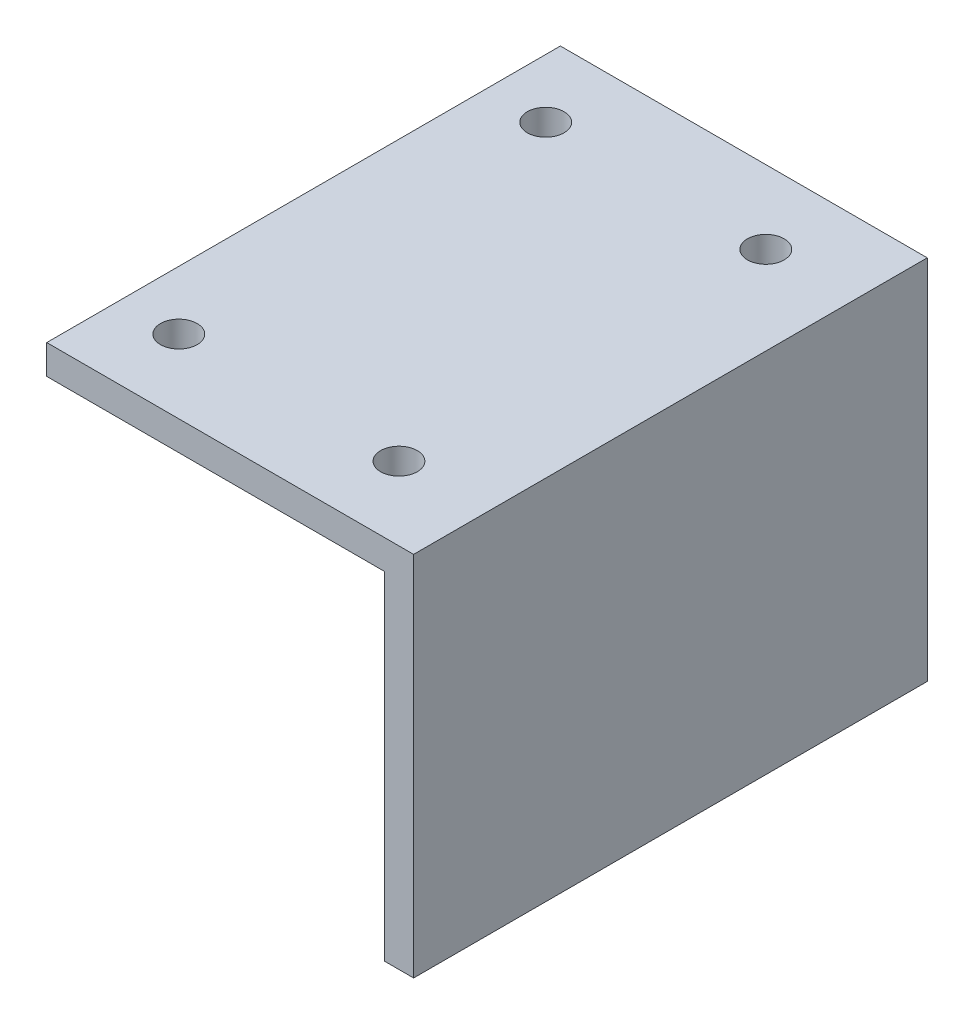
SolidWorks part; units mm, degrees
ref_plane "Alzado" through (0, 0, 0) normal (0, 0, 1) x (1, 0, 0)
ref_plane "Planta" through (0, 0, 0) normal (0, 1, 0) x (1, 0, 0)
ref_plane "Vista lateral" through (0, 0, 0) normal (1, 0, 0) x (0, 0, -1)
sketch "Croquis2" plane through (0, 0, 0) normal (0, 0, 1) x (1, 0, 0)
  line L0 (0, 0) -> (-50, 0)
  line L1 (0, 0) -> (0, -50)
  line L2 (-4, -4) -> (-4, -50)
  line L3 (-4, -4) -> (-50, -4)
  line L4 (-50, 0) -> (-50, -4)
  line L5 (-4, -50) -> (0, -50)
  dimension "D1" = 50
  dimension "D2" = 4
extrude "Saliente-Extruir1" add sketch "Croquis2" along normal blind 35 and the other way blind 35
sketch "Croquis3" plane through (0, -4, 0) normal (0, -1, 0) x (1, 0, 0)
  line L0 (-4, 0) -> (-50, 0) construction
  line L1 (-42, 25) -> (-12, 25) construction
  line L2 (-42, 25) -> (-42, -25) construction
  line L3 (-42, -25) -> (-12, -25) construction
  line L4 (-12, 25) -> (-12, -25) construction
  line L5 (-42, 25) -> (-12, -25) construction
  line L6 (-42, -25) -> (-12, 25) construction
  line L7 (-4, 35) -> (-4, -35) construction
  line L8 (-50, 35) -> (-50, -35) construction
  circle A0 centre (-12, 25) radius 2.5
  circle A1 centre (-12, -25) radius 2.5
  circle A2 centre (-42, 25) radius 2.5
  circle A3 centre (-42, -25) radius 2.5
  point P0 (-27, 0)
  dimension "D3" = 5
  dimension "D1" = 30
  dimension "D2" = 50
extrude "Cortar-Extruir1" cut sketch "Croquis3" against normal up to surface (4 mm away) up to face at (-25, 0, 0)
